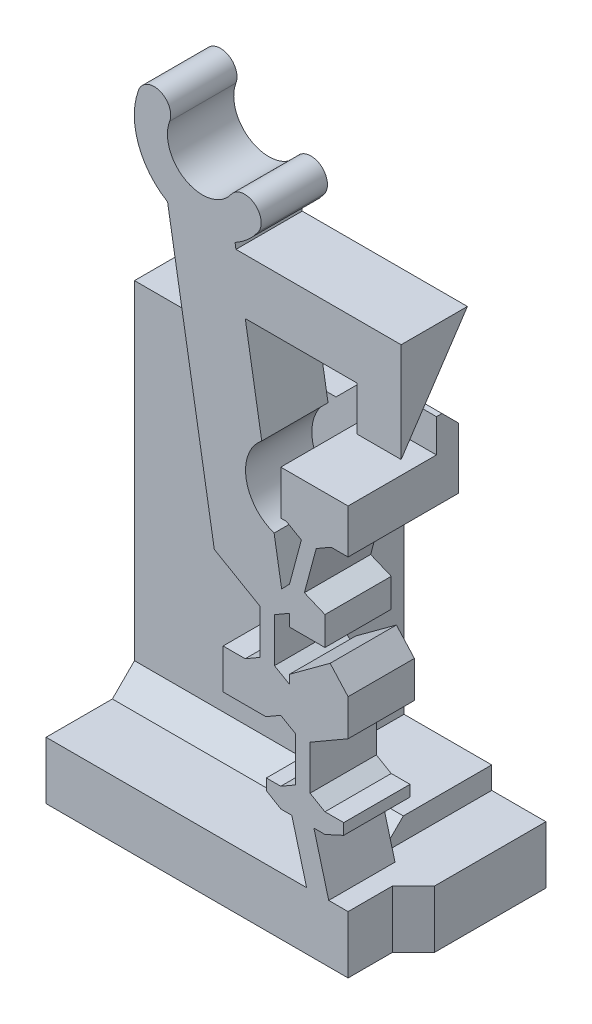
SolidWorks part; units mm, degrees
material "Nylon 6/12"
ref_plane "Front Plane" through (0, 0, 0) normal (0, 0, 1) x (1, 0, 0)
ref_plane "Top Plane" through (0, 0, 0) normal (0, 1, 0) x (1, 0, 0)
ref_plane "Right Plane" through (0, 0, 0) normal (1, 0, 0) x (0, 0, -1)
sketch "Sketch-SkeletonConfigUp" plane through (0, 0, 0) normal (0, 0, 1) x (1, 0, 0)
  line L0 (0, 0) -> (0, -50000) construction
  line L1 (0, 0) -> (4.5811, 6.2164) construction
  line L2 (9.8143, 13.3177) -> (4.5811, 13.945) construction
  line L3 (4.5811, 13.945) -> (2.9713, 10.4094) construction
  line L4 (2.9713, 10.4094) -> (4.5811, 6.2164) construction
  line L5 (4.5811, 13.945) -> (6.2429, 19.1409) construction
  line L6 (2.9713, 10.4094) -> (0.0405, 27.8193) construction
  line L7 (4.5811, 6.2164) -> (9.8143, 13.3177) construction
  line L8 (-587.3593, -797.0242) -> (9.8143, 13.3177) construction
  dimension "D2" = 7.7221
  dimension "D3" = 8.8212
  dimension "D4" = 5.2707
  dimension "D5" = 119.553
  dimension "D6" = 3.8848
  dimension "D7" = 5.4552
  dimension "D8" = 17.6549
  dimension "D9" = 4.4914
  dimension "D10" = 6.745
  dimension "D11" = 145.964
  dimension "D12" = 143.612
sketch "Sketch-SkeletonConfigDown" plane through (0, 0, 0) normal (0, 0, 1) x (1, 0, 0)
  line L0 (0, 0) -> (0, -50000) construction
  line L1 (0, 0) -> (4.5811, 6.2164) construction
  line L2 (9.8143, 13.3177) -> (4.5811, 13.945) construction
  line L3 (4.5811, 13.945) -> (6.1909, 10.4094) construction
  line L4 (6.1909, 10.4094) -> (4.5811, 6.2164) construction
  line L5 (4.5811, 13.945) -> (1.753, 18.6098) construction
  line L6 (6.1909, 10.4094) -> (-8.8652, 19.6294) construction
  line L7 (4.5811, 6.2164) -> (9.8143, 13.3177) construction
  line L8 (-589.9357, -800.5203) -> (9.8143, 13.3177) construction
  dimension "D2" = 7.7221
  dimension "D3" = 8.8212
  dimension "D4" = 5.2707
  dimension "D5" = 119.553
  dimension "D6" = 3.8848
  dimension "D7" = 5.4552
  dimension "D8" = 17.6549
  dimension "D9" = 4.4914
  dimension "D10" = 6.745
  dimension "D11" = 145.964
  dimension "D1" = 143.612
ref_plane "Plane-Cam Base" through (9.128, 0, 0) normal (1, 0, 0) x (0, 0, -1)
ref_plane "Plane-Down-to-Up Derailleur Clearance" through (6.628, 0, 0) normal (1, 0, 0) x (0, 0, -1)
ref_plane "Plane-Cam Cavity Roof" through (5.128, 0, 0) normal (1, 0, 0) x (0, 0, -1)
sketch "Sketch-SwitchBossUp" plane through (0, 0, 0) normal (0, 0, 1) x (1, 0, 0)
  line L0 (3.5811, 11.4759) -> (3.5811, 12.945) construction
  line L5 (5.5811, 12.5552) -> (5.5811, 11.263)
  line L7 (1.5115, 25.1048) -> (1.5536, 24.8548)
  line L8 (-0.4607, 24.7728) -> (1.6966, 11.9577) construction
  line L9 (2.9713, 10.4094) -> (0.0405, 27.8193) construction
  line L11 (0.1364, 21.2256) -> (2.1086, 21.5576) construction
  line L15 (6.628, -23.7286) -> (6.628, 23.7286) construction
  line L16 (2.9713, 10.4094) -> (4.5811, 6.2164) construction
  line L17 (3.5811, 12.945) -> (3.5811, 14.945) construction
  line L18 (5.5811, 12.945) -> (5.5811, 14.945) construction
  line L19 (4.2561, 13.945) -> (4.9061, 13.945) construction
  line L20 (3.5811, 14.945) -> (5.5811, 14.945) construction
  line L21 (3.5811, 12.945) -> (5.5811, 12.945) construction
  line L22 (4.5811, 12.945) -> (4.5811, 14.945) construction
  line L23 (4.5811, 6.2164) -> (8.5405, 7.1023) construction
  line L24 (1.9713, 9.4094) -> (1.9713, 11.4094) construction
  line L25 (3.9713, 9.4094) -> (3.9713, 11.4094) construction
  line L26 (3.9713, 9.4094) -> (1.9713, 9.4094) construction
  line L27 (1.9713, 11.4094) -> (3.9713, 11.4094) construction
  line L28 (3.5811, 7.2164) -> (5.5811, 7.2164) construction
  line L29 (3.5811, 7.2164) -> (3.5811, 5.2164) construction
  line L30 (5.5811, 7.2164) -> (5.5811, 5.2164) construction
  line L31 (3.5811, 5.2164) -> (5.5811, 5.2164) construction
  line L32 (4.9061, 6.2164) -> (4.2561, 6.2164) construction
  line L40 (3.2963, 10.4094) -> (2.6463, 10.4094) construction
  line L66 (0.0405, 27.8193) -> (0.0405, 50027.8193) construction
  line L75 (4.5811, 3.937) -> (5.251, 1.437) construction
  line L76 (5.5811, 11.263) -> (5.5811, 12.5552) construction
  line L77 (5.5811, 7.6061) -> (6.628, 8.2105)
  line L80 (5.8152, 10.763) -> (6.628, 9.8603)
  line L81 (9.128, 1033.2419) -> (9.128, 20.0586) construction
  line L85 (6.9307, 9.5241) -> (8.5405, 7.7363) construction
  line L88 (5.7256, 17.3347) -> (6.628, 17.3347)
  line L92 (3.7762, 8.3129) -> (6.9307, 9.5241) construction
  line L98 (1.9713, 9.0197) -> (0.9713, 9.0197)
  line L99 (0.9713, 9.0197) -> (0.9713, 7.2164)
  line L100 (0.9713, 7.2164) -> (2.9061, 7.2164)
  line L101 (4.5811, 6.2164) -> (6.9307, 9.5241) construction
  line L103 (0.0405, 27.8193) -> (1.9448, 26.4638) construction
  line L104 (6.9307, 9.5241) -> (8.5405, 7.7363) construction
  line L107 (1.9713, 9.4094) -> (1.9713, 9.0197) construction
  line L109 (0.0405, 27.8193) -> (-2.1498, 28.6358) construction
  line L111 (6.628, 9.8603) -> (6.628, 8.2105)
  line L112 (6.628, 9.8603) -> (6.9307, 9.5241) construction
  line L113 (2.9306, 4.8267) -> (2.9306, 4.3267)
  line L114 (7.3693, 7.7363) -> (7.3563, 7.7363) construction
  line L121 (5.751, -1.0859) -> (5.751, 1.437) construction
  line L122 (9.028, 22.3548) -> (9.028, 20.3548)
  line L127 (5.5811, 15.3347) -> (5.5811, 14.945) construction
  line L133 (2.9713, 10.4094) -> (6.1909, 10.4094) construction
  line L134 (4.5811, 10.4094) -> (4.5811, 13.945) construction
  line L135 (4.5811, 10.4094) -> (4.5811, 6.2164) construction
  line L137 (3.9713, 9.4094) -> (5.5811, 7.2164) construction
  line L139 (5.8152, 10.763) -> (3.9713, 9.4094)
  line L142 (3.0345, 1.437) -> (3.0345, -1.1653)
  line L143 (9.128, 20.0586) -> (9.128, 18.3333) construction
  line L145 (9.128, 16.6071) -> (9.128, -49992.4167) construction
  line L147 (5.5811, 11.263) -> (5.5811, 12.5552) construction
  line L150 (3.0345, -1.1653) -> (6.628, -1.1653)
  line L151 (4.0811, 3.937) -> (5.0811, 3.937) construction
  line L152 (4.5126, 14.945) -> (3.9767, 12.945)
  line L153 (5.1855, 14.945) -> (4.6496, 12.945)
  line L157 (3.5811, 17.3347) -> (3.5811, 15.3347)
  line L158 (5.8605, 15.3347) -> (6.628, 15.3347)
  line L162 (3.2963, 11.4094) -> (3.2963, 9.4094)
  line L164 (2.6463, 11.4094) -> (2.6463, 9.4094)
  line L169 (4.2561, 7.2164) -> (4.2561, 5.2164)
  line L170 (4.9061, 5.2164) -> (4.9061, 7.2164)
  line L175 (4.2561, 7.2164) -> (3.5811, 7.6061)
  line L176 (4.9061, 7.2164) -> (5.5811, 7.6061)
  line L177 (5.5811, 7.2164) -> (5.5811, 7.6061) construction
  line L179 (4.2561, 5.2164) -> (3.5811, 4.8267)
  line L180 (3.5811, 5.2164) -> (3.5811, 4.8267) construction
  line L181 (3.5811, 4.8267) -> (2.9306, 4.8267)
  line L183 (4.9061, 5.2164) -> (5.5811, 4.8267)
  line L184 (5.5811, 5.2164) -> (5.5811, 4.8267) construction
  line L186 (9.128, -23.7286) -> (9.128, 23.7286) construction
  line L187 (2.6463, 9.4094) -> (1.9713, 9.0197)
  line L188 (3.2963, 9.4094) -> (3.9713, 9.0197)
  line L189 (3.2963, 11.4094) -> (3.9713, 11.7991)
  line L190 (2.6463, 11.4094) -> (1.6966, 11.9577)
  line L191 (3.9713, 11.4094) -> (3.9713, 11.7991) construction
  line L192 (3.9713, 11.7991) -> (3.9713, 11.263)
  line L193 (4.6496, 12.945) -> (5.5811, 12.5552)
  line L194 (3.9767, 12.945) -> (3.6203, 12.5779)
  line L195 (3.9713, 11.263) -> (5.5811, 11.263)
  line L196 (3.9713, 9.4094) -> (3.9713, 9.0197)
  line L197 (3.5811, 7.2164) -> (3.5811, 7.6061) construction
  line L199 (3.5811, 7.6061) -> (2.9061, 7.2164)
  line L201 (2.9306, 4.3267) -> (2.9306, 3.937) construction
  line L202 (2.9306, 3.937) -> (4.0811, 3.937) construction
  line L205 (4.0811, 3.937) -> (3.585, 3.937)
  line L207 (9.128, 18.3333) -> (9.128, 16.6071) construction
  line L208 (6.628, -1.1653) -> (6.628, 1.437)
  line L209 (9.128, 20.0586) -> (9.128, 16.6071) construction
  line L211 (5.751, 1.437) -> (5.0811, 3.937)
  line L212 (4.751, 1.437) -> (4.0811, 3.937)
  line L214 (4.5126, 14.945) -> (3.8375, 15.3347)
  line L215 (3.8375, 15.3347) -> (3.5811, 15.3347)
  line L216 (5.1855, 14.945) -> (5.8605, 15.3347)
  line L217 (5.5811, 12.945) -> (5.5811, 12.5552) construction
  line L218 (5.1855, 14.945) -> (5.1855, 15.3347) construction
  line L219 (5.8605, 15.3347) -> (3.8375, 15.3347) construction
  line L221 (9.028, 22.3548) -> (9.028, 24.8548)
  line L224 (3.5811, 17.3347) -> (5.7256, 17.3347)
  line L232 (6.628, 15.3347) -> (6.628, 17.3347)
  line L236 (1.5536, 24.8548) -> (9.028, 24.8548)
  line L240 (5.0811, 3.937) -> (5.5824, 3.937)
  line L241 (5.5824, 3.937) -> (6.4306, 4.3267)
  line L248 (7.028, 22.3548) -> (1.9744, 22.3548)
  line L249 (1.9744, 22.3548) -> (2.7198, 17.9273)
  line L250 (9.028, 20.3548) -> (7.028, 20.3548)
  line L251 (7.028, 20.3548) -> (7.028, 22.3548)
  line L252 (3.2801, 14.5986) -> (3.6203, 12.5779)
  line L253 (4.2672, 14.0291) -> (4.895, 13.8608) construction
  line L254 (5.751, 1.437) -> (4.751, 1.437) construction
  line L255 (4.751, 1.437) -> (3.0345, 1.437) construction
  line L256 (4.5811, 6.2164) -> (4.5811, 3.937) construction
  line L257 (4.751, 1.437) -> (3.0345, 1.437)
  line L259 (5.751, 1.437) -> (6.628, 1.437)
  line L260 (3.585, 3.937) -> (2.9306, 4.3267)
  line L261 (1.6966, 11.9577) -> (0.5733, 12.6062)
  line L262 (0.5733, 12.6062) -> (-1.5413, 25.1678)
  line L367 (5.5811, 4.8267) -> (6.4306, 4.8267)
  line L368 (6.4306, 4.8267) -> (6.4306, 4.3267)
  arc A0 (1.5115, 25.1048) -> (2.5558, 26.0289) centre (0.0405, 27.8193) ccw
  arc A1 (-1.5413, 25.1678) -> (-2.8525, 28.8978) centre (0.0405, 27.8193) cw
  arc A2 (-2.8525, 28.8978) -> (-1.447, 28.3738) centre (-2.1498, 28.6358) cw
  arc A3 (2.5558, 26.0289) -> (1.3338, 26.8987) centre (1.9448, 26.4638) ccw
  arc A4 (-1.447, 28.3738) -> (1.3338, 26.8987) centre (0.0405, 27.8193) ccw
  arc A5 (3.5811, 12.945) -> (3.5811, 14.945) centre (3.1778, 13.945) ccw construction
  arc A6 (5.5811, 12.945) -> (5.5811, 14.945) centre (5.9843, 13.945) cw construction
  arc A7 (2.528, 9.9183) -> (1.9713, 11.4094) centre (1.568, 10.4094) ccw construction
  arc A8 (3.9713, 11.4094) -> (3.9713, 9.4094) centre (4.3745, 10.4094) ccw construction
  arc A9 (3.5811, 7.2164) -> (3.5811, 5.2164) centre (3.1779, 6.2164) cw construction
  arc A10 (5.5811, 7.2164) -> (5.5811, 5.2164) centre (5.9844, 6.2164) ccw construction
  circle A28 centre (0.0405, 27.8193) radius 2.3375 construction
  arc A29 (1.9713, 9.4094) -> (2.528, 9.9183) centre (1.568, 10.4094) ccw construction
  arc A30 (3.2801, 14.5986) -> (2.7198, 17.9273) centre (3.9114, 16.4164) cw
  arc A31 (-0.4607, 24.7728) -> (-1.5413, 25.1678) centre (0.0405, 27.8193) cw construction
  point P53 (4.5811, 13.945)
  point P63 (2.9713, 10.4094)
  point P93 (1.1225, 21.3916)
  dimension "D23" = 1.5875
  dimension "D24" = 0.75
  dimension "D2" = 2
  dimension "D5" = 2
  dimension "D8" = 42
  dimension "D16" = 42
  dimension "D27" = 120
  dimension "D28" = 120
  dimension "D29" = 120
  dimension "D30" = 120
  dimension "D31" = 120
  dimension "D32" = 120
  dimension "D33" = 120
  dimension "D34" = 120
  dimension "D17" = 0.5
  dimension "D21" = 2
  dimension "D38" = 2
  dimension "D39" = 0.5
  dimension "D40" = 60
  dimension "D41" = 1
  dimension "D42" = 45
  dimension "D43" = 120
  dimension "D10" = 15
  dimension "D25" = 15
  dimension "D26" = 120
  dimension "D35" = 120
  dimension "D83" = 3.5
  dimension "D14" = 2.5
  dimension "D15" = 0.25
  dimension "D7" = 2
  dimension "D9" = 2
  dimension "D6" = 0.65
  dimension "D12" = 1
  dimension "D13" = 18.5
  dimension "D18" = 2.5
  dimension "D19" = 0.65
  dimension "D20" = 1
extrude "Boss-Switch Body" add sketch "Sketch-SwitchBossUp" along normal blind 3
sketch "Sketch1" plane through (0, 0, 0) normal (0, 0, -1) x (-1, 0, 0)
  line L1 (-7.5811, -1.1653) -> (0.4122, -1.1653)
  line L2 (-7.5811, -1.1653) -> (-7.5811, 1.437)
  line L4 (0.4122, -1.1653) -> (0.4122, 1.437)
  line L5 (-3.5811, 18.8347) -> (-7.5811, 18.8347)
  line L10 (-7.5811, 18.8347) -> (-7.5811, 15.3347)
  line L11 (-4.751, 1.437) -> (-5.751, 1.437)
  line L12 (-7.5811, 15.3347) -> (-3.5811, 15.3347)
  line L13 (-4.751, 1.437) -> (-3.0345, 1.437)
  line L14 (-3.5811, 15.3347) -> (-3.5811, 18.8347)
  line L20 (-5.0811, 3.937) -> (-5.751, 1.437) construction
  line L22 (-3.0345, -1.1653) -> (-6.628, -1.1653) construction
  line L23 (-3.0345, 1.437) -> (0.4122, 1.437)
  line L24 (-5.751, 1.437) -> (-6.628, 1.437)
  line L25 (-6.628, 1.437) -> (-7.5811, 1.437)
  dimension "D1" = 3.5
extrude "Boss-Flange Width" add sketch "Sketch1" along normal blind 5
ref_plane "Plane-Sta2Sit Groove" through (0.0405, 0, 0) normal (1, 0, 0) x (0, 0, -1)
ref_plane "Plane-Cam Outer Surface" through (-12.0395, 0, 0) normal (1, 0, 0) x (0, 0, -1)
ref_plane "Plane-FlangeTop" through (-7.0395, 0, 0) normal (1, 0, 0) x (0, 0, -1)
sketch "Sketch2" plane through (-7.0395, 0, 0) normal (1, 0, 0) x (0, 0, -1)
  line L0 (5, 15.3347) -> (-3, 15.3347) construction
  line L1 (5, 17.3347) -> (1, 17.3347)
  line L2 (5, 17.3347) -> (5, 15.3347)
  line L3 (5, 15.3347) -> (1, 15.3347)
  line L4 (1, 17.3347) -> (1, 15.3347)
  line L5 (-3, -1.1653) -> (-3, 1.437) construction
  line L11 (5, 1.437) -> (-3, 1.437)
  line L12 (5, 1.437) -> (5, -1.1653)
  line L13 (5, -1.1653) -> (-3, -1.1653)
  line L14 (-3, 1.437) -> (-3, -1.1653)
  line L15 (0, 10.4094) -> (0, 27.8193) construction
  line L17 (5, 1.437) -> (5, -1.1653) construction
  line L18 (-3, 1.437) -> (0, 1.437) construction
  dimension "D1" = 1
  dimension "D2" = 2
extrude "Boss-Flange Height" add sketch "Sketch2" along normal up to surface (11.6675 mm away)
sketch "Sketch10" plane through (0, 15.3347, 0) normal (0, 1, 0) x (1, 0, 0)
  line L0 (9.128, -23.7286) -> (9.128, 23.7286) construction
  line L1 (7.5811, 5) -> (5.128, 5)
  line L2 (7.5811, 5) -> (7.5811, 2)
  line L3 (7.5811, 2) -> (5.128, 2)
  line L5 (4.628, 7) -> (4.628, 1) construction
  line L6 (3.5811, 1) -> (-7.0395, 1) construction
  line L8 (5.128, 5) -> (5.128, 2)
  dimension "D1" = 1
  dimension "D2" = 0.5
  dimension "D3" = 4.5
extrude "Cut-Up-To-Down Derailleur Clearance" cut sketch "Sketch10" along normal up to next
sketch "Sketch17" plane through (0, 15.3347, 0) normal (0, -1, 0) x (1, 0, 0)
  line L0 (5.128, -5) -> (-7.0395, -5)
  line L1 (5.128, -5) -> (-7.0395, -5) construction
  line L2 (-7.0395, -5) -> (-7.0395, -1)
  line L3 (-7.0395, -1) -> (5.128, -1)
  line L4 (5.128, -1) -> (5.128, -5)
  line L5 (-7.0395, -1) -> (-7.0395, -5) construction
extrude "Boss-Flange Support" add sketch "Sketch17" along normal up to surface (13.8977 mm away) up to face at (3.5343, 1.437, 0.2)
sketch "Sketch-HolePositions" plane through (0, -1.1653, 0) normal (0, -1, 0) x (1, 0, 0)
  line L0 (-7.0395, -3) -> (7.5811, -3) construction
  line L1 (7.5811, -5) -> (-7.0395, -5) construction
  line L2 (7.5811, -5) -> (7.5811, 0) construction
  line L4 (-7.0395, -22.2167) -> (-7.0395, 22.2167) construction
  point P6 (-5.0395, -3)
  point P7 (-0.5395, -3)
  dimension "D1" = 2
  dimension "D2" = 4.5
  dimension "D3" = 2
sketch "Sketch6" plane through (0, -1.1653, 0) normal (0, -1, 0) x (-1, 0, 0)
  point P0 (5.0395, 3)
  point P3 (0.5395, 3)
hole_wizard "Tap Drill for M2x0.4 Tap1" positions "Sketch6" profile "Sketch5" hole size "M2x0.4" standard "ANSI Metric" end condition through all
sketch "Sketch5" plane through (-5.0395, -1.1653, -3) normal (1, 0, 0) x (0, 0, -1)
  line L0 (0, 0) -> (0, 30.5511)
  line L1 (0, 30.5511) -> (0.8, 30.5511)
  line L2 (0.8, 30.5511) -> (0.8, 0)
  line L5 (0.8, 0) -> (0, 0)
  line L11 (0, -6.35) -> (0, 107.95) construction
  dimension "Thru Hole Dia." = 1.6
  dimension "Thru Hole Depth" = 30.5511
sketch "Sketch9" plane through (0, -1.1653, 0) normal (0, -1, 0) x (1, 0, 0)
  point P0 (-5.0395, -3)
  point P3 (-0.5395, -3)
hole_wizard "M2 Clearance Hole2" positions "Sketch9" profile "Sketch8" hole size "M2" standard "ANSI Metric"
sketch "Sketch8" plane through (-5.0395, -1.1653, -3) normal (1, 0, 0) x (0, 0, -1)
  line L0 (0, 0) -> (0, 15.721)
  line L1 (0, 15.721) -> (1.2, 15)
  line L2 (1.2, 15) -> (1.2, 0)
  line L5 (1.2, 0) -> (0, 0)
  line L10 (0, 15.721) -> (-1.2, 15) construction
  line L11 (0, -6.35) -> (0, 107.95) construction
  dimension "Hole Dia." = 2.4
  dimension "Hole Depth" = 15
  dimension "Drill Angle" = 118
sketch "Sketch-Measurements for Derailleur Ramps" [suppressed] plane through (0, 0, 0) normal (0, 0, 1) x (1, 0, 0)
  line L0 (3.184, 15.1695) -> (2.4687, 19.4188)
  line L1 (2.8264, 17.2941) -> (1.8402, 17.1281)
  line L2 (2.9713, 10.4094) -> (0.0405, 27.8193) construction
  line L3 (1.8402, 17.1281) -> (-1.3081, 15.0016)
  line L4 (6.1909, 10.4094) -> (-8.8652, 19.6294) construction
  line L5 (1.8402, 17.1281) -> (2.6012, 12.6077)
  line L6 (2.6012, 12.6077) -> (-1.3081, 15.0016)
  line L7 (0.2661, 16.0649) -> (0.2661, 17.1281)
  line L8 (0.2661, 17.1281) -> (1.8402, 17.1281)
  line L9 (6.1909, 10.4094) -> (2.9713, 10.4094)
  line L10 (5.386, 8.3129) -> (3.7762, 8.3129)
  line L11 (2.6116, 18.5698) -> (1.5115, 25.1048) construction
  line L12 (6.1909, 10.4094) -> (4.5811, 6.2164) construction
  line L13 (4.5811, 8.3129) -> (4.5811, 8.7912)
  line L14 (4.5811, 6.2164) -> (5.386, 8.3129)
  line L15 (2.9713, 10.4094) -> (4.5811, 6.2164) construction
  line L16 (3.7762, 8.3129) -> (4.5811, 6.2164)
  line L17 (5.386, 8.3129) -> (5.386, 8.7912)
  dimension "D1" = 1.5742
  dimension "D2" = 0.8049
ref_plane "Plane1" through (0, 7.1023, 0) normal (0, 1, 0) x (1, 0, 0)
ref_plane "Plane-Cantilever Cut" [suppressed] through (7.0848, 8.5204, -1.9058) normal (-0.6301, -0.7578, 0.1695) x (-0.7765, 0.6151, -0.1368)
sketch "Sketch14" [suppressed] plane through (7.0848, 8.5204, -1.9058) normal (-0.6301, -0.7578, 0.1695) x (-0.7765, 0.6151, -0.1368)
  line L0 (2.3023, -1.6911) -> (-0.3551, -1.6911)
  line L2 (2.3023, -4.3362) -> (2.3023, -1.6911)
  line L3 (-0.3551, -1.6911) -> (-0.3551, -4.4608)
  line L5 (-0.3551, -4.4608) -> (1.0087, -5.0843)
  line L6 (1.0087, -5.0843) -> (2.3023, -4.3362)
extrude "Cut-Down-to-Up Cantilever Slope" [suppressed] cut sketch "Sketch14" against normal up to next
ref_plane "Plane-Symmetry Plane" through (0, 0, 1.5) normal (0, 0, 1) x (1, 0, 0)
sketch "Sketch-Cable Center Point" plane through (0, 0, 1.5) normal (0, 0, 1) x (1, 0, 0)
  line L0 (0.0405, 27.8193) -> (0.1722, 27.0366)
  line L1 (2.9713, 10.4094) -> (0.0405, 27.8193) construction
  point P0 (0.0405, 27.8193)
  dimension "D1" = 0.7937
chamfer "Chamfer-Flange Support" distance 1.5 angle 45 1 edges at (3.5811, 17.3347, -3)
chamfer "Chamfer-Flange Support 2" distance 1.5 angle 45 2 edges at (5.128, 17.0847, -2) (5.128, 15.3347, -1.5)
chamfer "Chamfer-Flange Support 3" distance 1 angle 45 1 edges at (-0.9558, 1.437, -1)
chamfer "Chamfer7" [suppressed] distance 1 angle 45
sketch "Sketch23" plane through (0, 0, -1) normal (0, 0, 1) x (1, 0, 0)
  line L0 (5.128, 2.437) -> (1.1605, 2.437)
  line L1 (-7.0395, 2.437) -> (5.128, 2.437) construction
  line L2 (1.1605, 2.437) -> (1.1605, 13.8347)
  line L3 (1.1605, 13.8347) -> (5.128, 13.8347)
  line L4 (5.128, 13.8347) -> (5.128, 2.437)
  line L5 (0.6605, -1.1653) -> (0.6605, 13.8347) construction
  dimension "D1" = 0.5
extrude "Cut-Gap for Printing" cut sketch "Sketch23" against normal through all
sketch "Sketch25" plane through (0, 0, 0) normal (0, 0, 1) x (1, 0, 0)
  line L0 (6.628, 15.3347) -> (7.5811, 15.3347)
  line L1 (7.5811, 15.3347) -> (7.5811, 18.8347)
  line L2 (7.5811, 18.8347) -> (6.628, 18.8347)
  line L3 (6.628, -23.7286) -> (6.628, 23.7286) construction
  line L4 (7.5811, 18.8347) -> (3.5811, 18.8347) construction
  line L5 (6.628, 18.8347) -> (6.628, 15.3347)
  line L6 (7.5811, 18.8347) -> (7.5811, 15.3347) construction
extrude "Cut-Derailleur Clearance" cut sketch "Sketch25" against normal through all
chamfer "Chamfer8" distance 1 angle 45 1 edges at (6.628, 0.1359, 0)
ref_plane "Plane2" through (-3.0866, 5.589, 8.3835) normal (0.2929, -0.5304, -0.7956) x (-0.9561, -0.1625, -0.2437)
sketch "Sketch26" plane through (-3.0866, 5.589, 8.3835) normal (0.2929, -0.5304, -0.7956) x (-0.9561, -0.1625, -0.2437)
  line L0 (-7.553, 20.6804) -> (-7.553, 14.9094)
  line L1 (-12.6703, 20.6804) -> (-5.5238, 20.6804) construction
  line L3 (-7.553, 14.9094) -> (-20.0302, 14.9094)
  line L4 (-20.0302, 14.9094) -> (-20.0302, 20.6804)
  line L5 (-20.0302, 20.6804) -> (-7.553, 20.6804)
extrude "Cut-Up-to-Down Cantilever Slope" cut sketch "Sketch26" along normal up to next
sketch "Sketch27" plane through (5.128, 0, 0) normal (1, 0, 0) x (0, 0, -1)
  line L0 (3.5, 18.8347) -> (3.5, 13.8347) construction
  line L1 (2.5, 18.8347) -> (5, 18.8347)
  line L2 (2.5, 18.8347) -> (2.5, 13.8347)
  line L3 (2.5, 13.8347) -> (5, 13.8347)
  line L4 (5, 18.8347) -> (5, 13.8347)
  dimension "D1" = 1
extrude "Cut-Wide Derailleur Clearance" cut sketch "Sketch27" against normal blind 4 and the other way through all
chamfer "Chamfer9" distance 1.25 angle 45 1 edges at (4.8545, 18.8347, -2.5)
sketch "Sketch28" plane through (0, 0, -1) normal (0, 0, 1) x (1, 0, 0)
  line L0 (3.5811, 18.8347) -> (6.628, 18.8347)
  line L1 (6.628, 18.8347) -> (6.628, 17.3347)
  line L2 (6.628, 17.3347) -> (3.5811, 17.3347)
  line L3 (3.5811, 17.3347) -> (3.5811, 18.8347)
extrude "Cut-Extrude1" cut sketch "Sketch28" along normal up to surface (1 mm away) up to face at (5.1045, 18.0847, 0)
equation "\"axle-diameter\"=2"
equation "\"switch-thickness\"=12"
equation "\"base-width\"=4.0"
equation "\"axle-bushing-radius\"=3"
equation "\"clearance\"= 0.25"
equation "\"arm-width\"=1.5"
equation "\"min-diameter\"=70"
equation "\"alpha\"=143.6120"
equation "\"gamma\"=119.5526"
equation "\"delta\"=145.9637"
equation "\"epsilon\"=6.7452"
equation "\"l_AB\"=8.8212"
equation "\"l_AC\"=4.4914"
equation "\"l_BD\"=5.2707"
equation "\"l_CD\"=3.8848"
equation "\"l_CE\"=17.6549"
equation "\"l_DF\"=5.4552"
equation "\"l_OA\"=7.7221"
equation "\"D2@Sketch-SkeletonConfigUp\" = \"l_OA\""
equation "\"D3@Sketch-SkeletonConfigUp\" = \"l_AB\""
equation "\"D4@Sketch-SkeletonConfigUp\" = \"l_BD\""
equation "\"D5@Sketch-SkeletonConfigUp\" = \"gamma\""
equation "\"D6@Sketch-SkeletonConfigUp\" = \"l_CD\""
equation "\"D7@Sketch-SkeletonConfigUp\" = \"l_DF\""
equation "\"D8@Sketch-SkeletonConfigUp\" = \"l_CE\""
equation "\"D9@Sketch-SkeletonConfigUp\" = \"l_AC\""
equation "\"D_groove\"=3.175"
equation "\"D7@Sketch-SkeletonConfigDown\" = \"l_DF\""
equation "\"D6@Sketch-SkeletonConfigDown\" = \"l_CD\""
equation "\"D2@Sketch-SkeletonConfigDown\" = \"l_OA\""
equation "\"D3@Sketch-SkeletonConfigDown\" = \"l_AB\""
equation "\"D9@Sketch-SkeletonConfigDown\" = \"l_AC\""
equation "\"D8@Sketch-SkeletonConfigDown\" = \"l_CE\""
equation "\"D5@Sketch-SkeletonConfigDown\" = \"gamma\""
equation "\"D4@Sketch-SkeletonConfigDown\" = \"l_BD\""
equation "\"D1@Sketch-SkeletonConfigDown\" = \"alpha\""
equation "\"hinge_length\"=1.5"
equation "\"hinge_depth\"=0.25"
equation "\"D10@Sketch-SkeletonConfigUp\"=\"epsilon\""
equation "\"D11@Sketch-SkeletonConfigUp\"=\"delta\""
equation "\"D12@Sketch-SkeletonConfigUp\"=\"alpha\""
equation "\"D11@Sketch-SkeletonConfigDown\"=\"delta\""
equation "\"D10@Sketch-SkeletonConfigDown\"=\"epsilon\""
equation "\"EE_dx\"=8.9056"
equation "\"EE_dy\"=8.1898"
equation "\"r_groove\"=\"D_groove\"/2"
equation "\"t_wall\"=25.4/16"
equation "\"width_lower\"=\"D_groove\"+\"t_wall\""
equation "\"cable_to_bottom\"=30.6257"
equation "\"switch_EE-up_base_dy\"=24"
equation "\"switch_EE-down_base_dy\"=16"
equation "\"D_axle\"=25.4/8"
equation "\"D_up_to_down\"=16"
equation "\"D_down_to_up\"=25"
equation "\"t_cam_base\"=7.5"
equation "\"D23@Sketch-SwitchBossUp\"=\"D_groove\"/2"
equation "\"D1@Sketch-Cable Center Point\"=\"D_groove\"/4"
